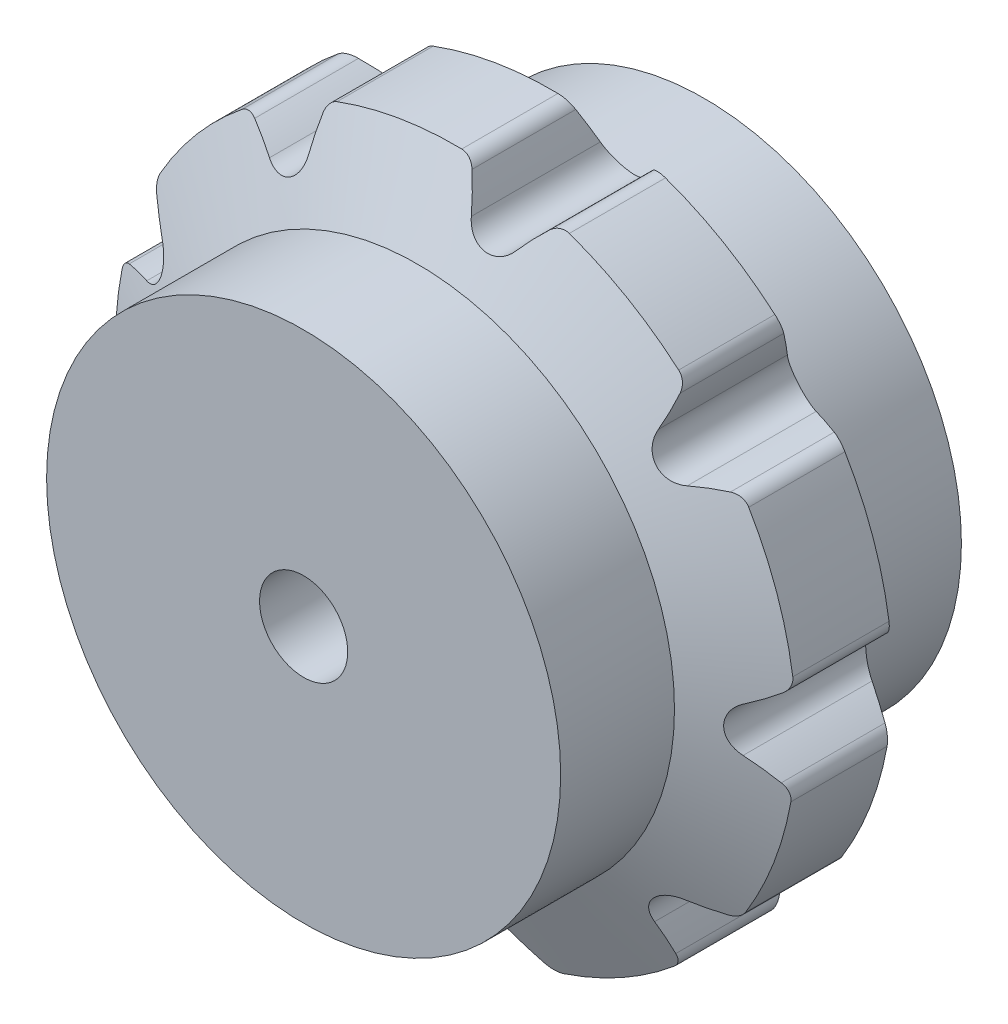
SolidWorks part; units mm, degrees
material "ABS"
ref_plane "Front" through (0, 0, 0) normal (0, 0, 1) x (1, 0, 0)
ref_plane "Top" through (0, 0, 0) normal (0, 1, 0) x (1, 0, 0)
ref_plane "Right" through (0, 0, 0) normal (1, 0, 0) x (0, 0, -1)
ref_axis "Axis1" through (0, 0, -80.9) along (0, 0, 1)
sketch "Sketch2" plane through (0, 0, 0) normal (0, 0, 1) x (1, 0, 0)
  line L0 (12.7692, 11.8308) -> (17.3864, -0.8551)
  line L1 (-9.8678, 17.0916) -> (-18.5455, 6.75) construction
  line L2 (-18.5455, 6.75) -> (-18.5455, -6.75) construction
  line L3 (-18.5455, -6.75) -> (-9.8678, -17.0916) construction
  line L4 (-9.8678, -17.0916) -> (3.4271, -19.4359) construction
  line L5 (3.4271, -19.4359) -> (15.1184, -12.6859) construction
  line L6 (15.1184, -12.6859) -> (19.7357, 0) construction
  line L7 (19.7357, 0) -> (15.1184, 12.6859) construction
  line L8 (15.1184, 12.6859) -> (3.4271, 19.4359) construction
  line L9 (3.4271, 19.4359) -> (-9.8678, 17.0916) construction
  line L10 (15.1184, 12.6859) -> (17.9375, 13.7119)
  line L11 (17.9375, 13.7119) -> (22.5548, 1.0261)
  line L12 (22.5548, 1.0261) -> (19.7357, 0)
  circle A0 centre (0, 0) radius 18.5455 construction
  circle A1 centre (0, 0) radius 19.7357 construction
  circle A2 centre (15.1184, 12.6859) radius 2.5
  circle A3 centre (19.7357, 0) radius 2.5
  dimension "D2" = 39.4714
  dimension "D4" = 3
  dimension "D1" = 13.5
  dimension "D3" = 2.5
sketch "Sketch1" plane through (0, 0, 0) normal (0, 1, 0) x (1, 0, 0)
  line L0 (0, 0) -> (0, -50000) construction
  line L1 (3, 12.5) -> (16.0357, 12.5)
  line L2 (16.0357, 12.5) -> (16.0357, 5.4)
  line L3 (16.0357, 5.4) -> (21.2357, 3)
  line L4 (21.2357, 3) -> (21.2357, -3)
  line L5 (21.2357, -3) -> (16.0357, -5.4)
  line L6 (16.0357, -5.4) -> (16.0357, -12.5)
  line L7 (16.0357, -12.5) -> (12.0357, -12.5)
  line L8 (12.0357, -12.5) -> (10, -2.5)
  line L9 (10, -2.5) -> (3, -2.5)
  line L10 (3, -2.5) -> (3, 12.5)
  line L11 (21.2357, 0) -> (0, 0) construction
  line L12 (19.7357, 3.6923) -> (19.7357, -3.6923) construction
  point P19 (19.7357, 0)
  dimension "D1" = 6
  dimension "D2" = 10.8
  dimension "D3" = 25
  dimension "D4" = 3.7
  dimension "D5" = 6
  dimension "D6" = 20
  dimension "D7" = 4
  dimension "D8" = 15
  dimension "D9" = 1.5
  dimension "D10" = 42.4714
  dimension "D11" = 32.0714
revolve "Revolve1" add sketch "Sketch1" angle 360 about L0 other way angle 360
sketch "Sketch3" plane through (0, 0, 12.5) normal (0, 0, 1) x (1, 0, 0)
  line L0 (0, 0) -> (21.2357, 0) construction
  circle A0 centre (19.7357, 0) radius 1.6 construction
  circle A1 centre (0, 0) radius 19.7357 construction
  arc A2 (20.9606, 3.4072) -> (20.9606, -3.4072) centre (0, 0) cw
  circle A3 centre (0, 0) radius 21.2357 construction
  arc A4 (18.9656, 1.4025) -> (18.9656, -1.4025) centre (19.7357, 0) ccw
  arc A5 (20.9606, 3.4072) -> (20.5789, 2.4508) centre (19.9735, 3.2467) cw
  arc A6 (20.5789, 2.4508) -> (18.9656, 1.4025) centre (12.7085, 12.7976) cw
  arc A7 (20.5789, -2.4508) -> (18.9656, -1.4025) centre (12.7085, -12.7976) ccw
  arc A8 (20.9606, -3.4072) -> (20.5789, -2.4508) centre (19.9735, -3.2467) ccw
  circle A9 centre (0, 0) radius 18.0357 construction
  circle A10 centre (0, 0) radius 16.0357 construction
  dimension "D1" = 3.2
  dimension "D3" = 1
  dimension "D4" = 13
  dimension "D2" = 2
extrude "Cut-Extrude1" cut sketch "Sketch3" against normal through all
sketch "Sketch4" plane through (0, 0, 12.5) normal (0, 0, 1) x (1, 0, 0)
  line L0 (0, -16.0357) -> (0, 22.3368)
  line L1 (0, -16.0357) -> (0, -23.3005)
  circle A0 centre (0, 0) radius 16.0357 construction
  circle A1 centre (0, 0) radius 16.0357 construction
sketch "Sketch5" plane through (0, 0, 0) normal (1, 0, 0) x (0, 0, -1)
  line L0 (-12.5, 22.251) -> (13.794, 22.251)
  line L1 (-12.5, -16.0357) -> (-12.5, 22.3368) construction
  line L2 (13.794, 22.251) -> (13.794, -22.7901)
  line L3 (13.794, -22.7901) -> (-12.5, -23.3005)
  line L4 (-12.5, -16.0357) -> (-12.5, -23.3005) construction
ref_plane "Plane1" through (0, 0, 0) normal (-1, 0, 0) x (0, 0, 1)
sketch "Sketch6" plane through (0, 0, 0) normal (-1, 0, 0) x (0, 0, 1)
  line L1 (12.5, -16.0357) -> (12.5, 22.3368) construction
  line L2 (12.5, 3) -> (12.5, 12.0357)
  line L4 (12.5, -3) -> (12.5, -12.0357)
  line L7 (-12.5, 0) -> (12.5, 0)
  line L8 (-12.5, -3) -> (12.5, -3)
  line L9 (-12.5, 3) -> (12.5, 3)
  line L20 (3, 21.2357) -> (-3, 21.2357)
  line L21 (-5.4, 16.0357) -> (-12.5, 16.0357)
  line L22 (-3, 21.2357) -> (-5.4, 16.0357)
  line L23 (5.4, 16.0357) -> (3, 21.2357)
  line L24 (12.5, 16.0357) -> (5.4, 16.0357)
  line L25 (12.5, 12.0357) -> (12.5, 16.0357)
  line L29 (-12.5, 16.0357) -> (-12.5, 3)
  line L30 (-12.5, -3) -> (-12.5, -16.0357)
  line L34 (12.5, -16.0357) -> (12.5, -12.0357)
  line L35 (5.4, -16.0357) -> (12.5, -16.0357)
  line L36 (3, -21.2357) -> (5.4, -16.0357)
  line L37 (-5.4, -16.0357) -> (-3, -21.2357)
  line L38 (-12.5, -16.0357) -> (-5.4, -16.0357)
  line L39 (-3, -21.2357) -> (3, -21.2357)
revolve "Revolve5" add sketch "Sketch6" angle 360 about L7 reverse direction yes
pattern_circular "CirPattern1" count 10 over 359 about axis through (0, 0, -80.9) along (0, 0, 1) of "Cut-Extrude1"
sketch "Sketch7" plane through (0, 0, -12.5) normal (0, 0, -1) x (-1, 0, 0)
  circle A0 centre (0, 0) radius 3
  circle A5 centre (0, 0) radius 2.75
  point P28 (0, 0)
extrude "Boss-Extrude1" add sketch "Sketch7" against normal blind 25
extrude "Boss-Extrude2" add sketch "Sketch7<2>" against normal blind 25 contours A0
sketch "Sketch7<2>" plane through (0, 0, -12.5) normal (0, 0, -1) x (-1, 0, 0) same geometry as "Sketch7"
extrude "Cut-Extrude2" cut sketch "Sketch7<3>" against normal through all contours A5
sketch "Sketch7<3>" plane through (0, 0, -12.5) normal (0, 0, -1) x (-1, 0, 0) same geometry as "Sketch7"
